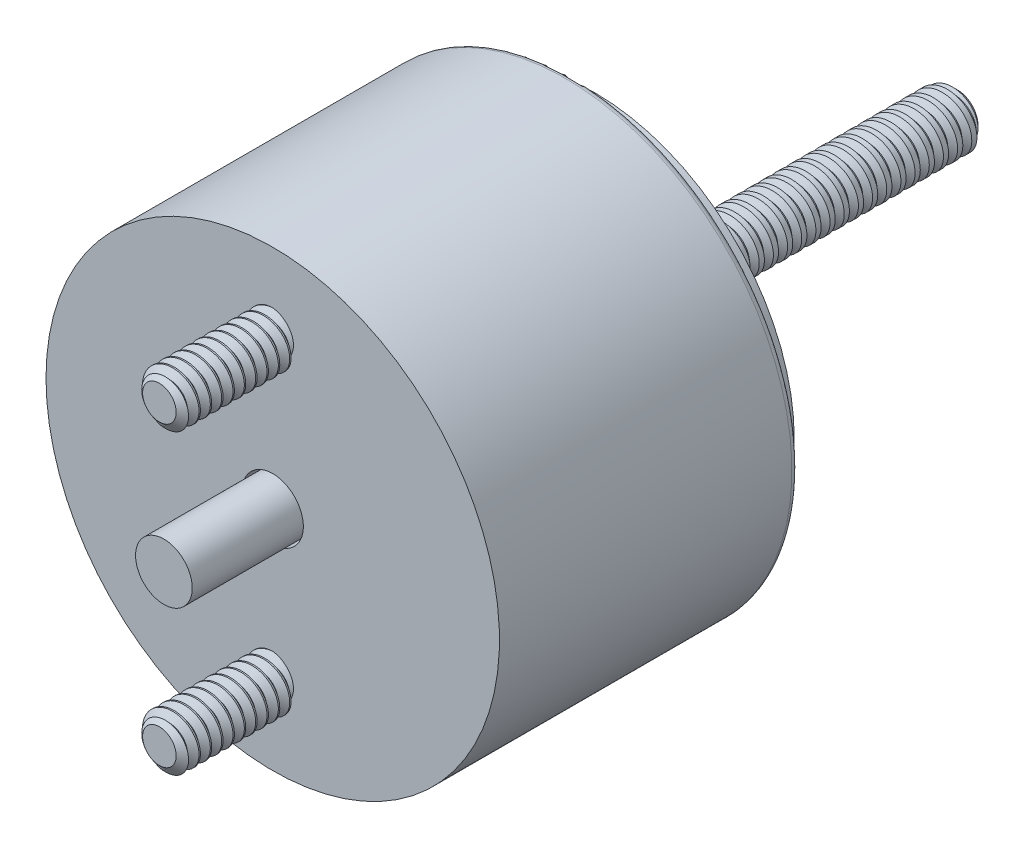
SolidWorks part; units mm, degrees
ref_plane "Front Plane" through (0, 0, 0) normal (0, 0, 1) x (1, 0, 0)
ref_plane "Top Plane" through (0, 0, 0) normal (0, 1, 0) x (1, 0, 0)
ref_plane "Right Plane" through (0, 0, 0) normal (1, 0, 0) x (0, 0, -1)
sketch "Sketch0" plane through (0, 0, 0) normal (1, 0, 0) x (0, 0, -1)
  line L0 (0, 0) -> (16.764, 0) construction
  line L1 (0, 0) -> (-13.716, 0) construction
  line L2 (16.764, 12.7) -> (16.764, -12.7) construction
  line L3 (0, 8.3312) -> (0, -8.3312) construction
  line L4 (-13.716, 1.5875) -> (-13.716, -1.5875) construction
  line L5 (-13.716, 0) -> (-6.096, 0) construction
  line L6 (16.764, 0) -> (30.734, 0) construction
  line L7 (0, 8.3312) -> (-6.35, 8.3312) construction
  line L8 (-6.35, 9.7536) -> (-6.35, 6.9088) construction
  line L9 (30.734, 1.7526) -> (30.734, -1.7526) construction
  line L10 (18.034, 11.176) -> (18.034, -11.176) construction
  point P15 (18.034, 0)
  dimension "D1" = 1.27
  dimension "Lg." = 16.764
  dimension "Dia." = 25.4
  dimension "Rod Dia." = 3.175
  dimension "A" = 13.716
  dimension "Stud C-C" = 16.6624
  dimension "Stroke" = 7.62
  dimension "B" = 13.97
  dimension "Stud Lg." = 6.35
  dimension "Stud OD" = 2.8448
  dimension "OAL" = 44.45
  dimension "D2" = 22.352
  dimension "Thread OD" = 3.5052
sketch "Sketch1" plane through (0, 0, 0) normal (1, 0, 0) x (0, 0, -1)
  line L0 (16.764, 0) -> (0, 0) construction
  line L1 (16.383, 12.7) -> (0, 12.7)
  line L2 (18.034, 11.176) -> (18.034, 1.7145)
  line L3 (0, 0) -> (0, 1.7145) construction
  line L5 (16.764, 0) -> (16.764, 12.319) construction
  line L6 (17.018, 11.176) -> (17.018, 10.922)
  line L7 (17.018, 10.922) -> (16.764, 10.922)
  line L8 (16.764, 10.922) -> (16.764, 12.319)
  line L9 (0, 12.7) -> (0, 1.7145)
  line L10 (17.018, 11.176) -> (18.034, 11.176)
  line L12 (0, 1.7145) -> (18.034, 1.7145)
  arc A1 (16.764, 12.319) -> (16.383, 12.7) centre (16.383, 12.319) ccw
  dimension "D1" = 0.381
  dimension "D4" = 0.127
  dimension "D2" = 0.254
  dimension "D3" = 0.254
revolve "Revolve1" add sketch "Sketch1" angle 360 mid plane about L0
sketch "Sketch2" plane through (0, 0, 0) normal (1, 0, 0) x (0, 0, -1)
  line L0 (-13.716, 0) -> (30.734, 0) construction
  line L2 (30.734, 0) -> (-13.716, 0)
  line L3 (30.734, 0) -> (30.734, 1.5875)
  line L4 (30.734, 1.5875) -> (-13.716, 1.5875)
  line L5 (-13.716, 0) -> (-13.716, 1.5875)
  line L8 (30.734, 1.7526) -> (30.734, -1.7526) construction
revolve "Revolve2" add sketch "Sketch2" angle 360 mid plane about L2
sketch "Sketch3" plane through (0, 0, -30.734) normal (0, 0, 1) x (1, 0, 0)
  circle A1 centre (0, 0) radius 1.7526
  point P1 (0, 1.7526)
curve "Helix/Spiral1" pitch 0.7937 height 22.3837 radius 1.7526 centre (0, 0, -30.734) axis (0, 0, 1) start towards (0, 1, 0) parameters "Pitch"=0.7937
sketch "Sketch4" plane through (0, 0, 0) normal (1, 0, 0) x (0, 0, -1)
  line L0 (30.6844, 1.8385) -> (31.4781, 1.8385) construction
  line L1 (31.4781, 1.8385) -> (31.0813, 1.1511) construction
  line L2 (31.0813, 1.1511) -> (30.6844, 1.8385) construction
  line L3 (31.0317, 1.237) -> (31.1309, 1.237) construction
  line L4 (30.734, 1.7526) -> (31.4285, 1.7526) construction
  line L5 (31.0813, 1.1511) -> (31.0813, 1.237) construction
  line L6 (31.0813, 1.7526) -> (31.0813, 1.8385) construction
  line L7 (31.0317, 1.237) -> (31.1309, 1.237)
  line L8 (31.1309, 1.237) -> (31.4533, 1.7956)
  line L9 (31.4533, 1.7956) -> (30.7092, 1.7956)
  line L10 (30.7092, 1.7956) -> (31.0317, 1.237)
  line L11 (31.0813, 1.1511) -> (31.0813, -1.5875) construction
  line L12 (31.0813, -1.5875) -> (30.2875, -1.5875) construction
  line L13 (30.2875, -1.5875) -> (29.4938, -1.5875) construction
  line L14 (29.4938, -1.5875) -> (28.7, -1.5875) construction
  line L15 (-13.716, -1.5875) -> (30.734, -1.5875) construction
  line L16 (28.7, -1.5875) -> (36.32, -1.5875) construction
  line L17 (-13.716, 0) -> (-6.096, 0) construction
  point P15 (31.0813, 1.7956)
  dimension "D1" = 0.7937
  dimension "D2" = 0.0992
sweep "Cut-Sweep1" cut profiles "Sketch4" path "Helix/Spiral1" align with end faces yes
sketch "Sketch5" plane through (0, 0, -30.734) normal (0, 0, -1) x (-1, 0, 0)
  circle A0 centre (0, 0) radius 1.1511
extrude "Cut-Extrude1" cut sketch "Sketch5" against normal blind 3.175 draft 45 flip side to cut
sketch "Sketch6" plane through (0, 0, 0) normal (0, 0, 1) x (1, 0, 0)
  circle A0 centre (0, 8.3312) radius 1.4224
extrude "Boss-Extrude1" add sketch "Sketch6" along normal up to vertex (6.35 mm away) separate body up to point (0, 9.7536, 6.35)
sketch "Sketch7" plane through (0, 0, 6.35) normal (0, 0, 1) x (1, 0, 0)
  circle A1 centre (0, 8.3312) radius 1.4224
  circle A2 centre (0, 8.3312) radius 1.4224
  point P0 (0, 9.7536)
  dimension "D1" = 0
curve "Helix/Spiral2" pitch 0.635 height 6.985 turns 11 parameters "Pitch"=0.635
sketch "Sketch8" plane through (0, 0, 0) normal (1, 0, 0) x (0, 0, -1)
  line L0 (-6.9453, 9.8223) -> (-6.3103, 9.8223) construction
  line L1 (-6.3103, 9.8223) -> (-6.6278, 9.2724) construction
  line L2 (-6.6278, 9.2724) -> (-6.9453, 9.8223) construction
  line L3 (-6.6675, 9.3412) -> (-6.5881, 9.3412) construction
  line L4 (-6.35, 9.7536) -> (-6.9056, 9.7536) construction
  line L5 (-6.6278, 9.2724) -> (-6.6278, 9.2037) construction
  line L6 (-6.6278, 9.2724) -> (-6.6278, 9.3412) construction
  line L7 (-6.6278, 9.7536) -> (-6.6278, 9.8223) construction
  line L8 (-6.9255, 9.788) -> (-6.6675, 9.3412)
  line L9 (-6.6675, 9.3412) -> (-6.5881, 9.3412)
  line L10 (-6.5881, 9.3412) -> (-6.3302, 9.788)
  line L11 (-6.3302, 9.788) -> (-6.9255, 9.788)
  point P15 (-6.6278, 9.788)
  dimension "D1" = 0.635
  dimension "D2" = 0.0794
sweep "Cut-Sweep2" cut profiles "Sketch8" path "Helix/Spiral2" align with end faces yes
sketch "Sketch9" plane through (0, 0, 6.35) normal (0, 0, 1) x (1, 0, 0)
  circle A1 centre (0, 8.3312) radius 0.9412
extrude "Cut-Extrude2" cut sketch "Sketch9" against normal through all draft 55 flip side to cut
pattern_linear "LPattern1" count 2 spacing 16.6624 along (0, -1, 0) of bodies 117
combine bodies "Combine1" operation type add bodies to combine 102 117 118
move or copy body "Body-Move/Copy1" bodies to move or copy 112 copy no translate (0, 0, -7.62)
sketch "SketchX" plane through (0, 0, 0) normal (1, 0, 0) x (0, 0, -1)
  line L0 (-6.096, 1.5875) -> (-13.716, 1.5875)
  line L2 (-13.716, 1.5875) -> (-13.716, -1.5875)
  line L3 (-13.716, -1.5875) -> (-6.096, -1.5875)
equation "\"D3@Helix/Spiral1\" = \"Pitch@Helix/Spiral1\" + \"B@Sketch0\" + \"Stroke@Sketch0\""
equation "\"D1@Sketch4\" = \"Pitch@Helix/Spiral1\""
equation "\"D2@Sketch4\" = \"D1@Sketch4\" / 8"
equation "\"D3@Helix/Spiral2\" = \"Pitch@Helix/Spiral2\" + \"Stud Lg.@Sketch0\""
equation "\"D1@Sketch8\" = \"Pitch@Helix/Spiral2\""
equation "\"D2@Sketch8\" = \"D1@Sketch8\" / 8"
equation "\"D3@LPattern1\" = \"Stud C-C@Sketch0\""
